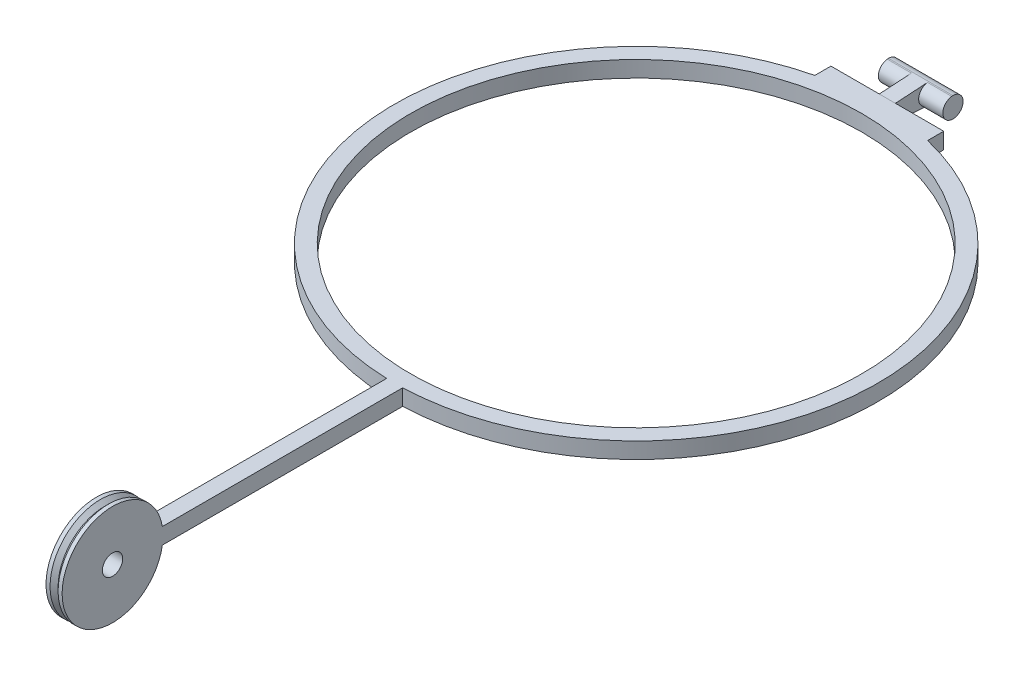
SolidWorks part; units mm, degrees
ref_plane "Front Plane" through (0, 0, 0) normal (0, 0, 1) x (1, 0, 0)
ref_plane "Top Plane" through (0, 0, 0) normal (0, 1, 0) x (1, 0, 0)
ref_plane "Right Plane" through (0, 0, 0) normal (1, 0, 0) x (0, 0, -1)
sketch "Sketch1" plane through (0, 0, 0) normal (0, 0, 1) x (1, 0, 0)
  line L0 (0, 0) -> (11.6505, 0) construction
  line L1 (0, 4) -> (6.35, 4)
  line L2 (0, 0) -> (0, 4) construction
  line L3 (0, 4) -> (0, 19.875)
  line L6 (6.35, 19.875) -> (6.35, 4)
  line L7 (3.175, 4) -> (3.175, 18.2875) construction
  line L8 (0, 19.875) -> (1.5875, 19.875)
  line L9 (1.5875, 19.875) -> (3.175, 18.2875)
  line L10 (4.7625, 19.875) -> (3.175, 18.2875)
  line L11 (6.35, 19.875) -> (4.7625, 19.875)
  dimension "D1" = 6.35
  dimension "D2" = 8
  dimension "D3" = 1.5875
  dimension "D4" = 15.875
  dimension "D5" = 1.5875
revolve "Revolve1" add sketch "Sketch1" angle 360 about L0
sketch "Sketch2" plane through (6.35, 0, 0) normal (1, 0, 0) x (0, 0, -1)
  line L0 (0, 0) -> (304.8, 0) construction
  line L1 (20.0281, 3.175) -> (304.8, 3.175)
  line L2 (304.8, 3.175) -> (304.8, 0)
  line L3 (20.0281, -3.175) -> (304.8, -3.175)
  line L4 (304.8, -3.175) -> (304.8, 0)
  circle A0 centre (0, 0) radius 4 construction
  circle A1 centre (0, 0) radius 4
  arc A7 (17.5856, 5.018) -> (17.5856, -5.018) centre (0, 0) ccw
  arc A8 (20.0281, -3.175) -> (17.5856, -5.018) centre (20.0281, -5.715) ccw
  arc A9 (20.0281, 3.175) -> (17.5856, 5.018) centre (20.0281, 5.715) cw
  circle A10 centre (0, 0) radius 18.2875 construction
  dimension "D3" = 2.54
  dimension "D1" = 304.8
  dimension "D2" = 6.35
extrude "Boss-Extrude1" add sketch "Sketch2" against normal up to surface (6.35 mm away) up to face at (0, 0, 4)
sketch "Sketch5" plane through (0, 3.175, 0) normal (0, 1, 0) x (1, 0, 0)
  line L0 (6.35, 304.8) -> (6.35, 20.0281) construction
  line L1 (0, 304.8) -> (6.35, 304.8)
  line L2 (0, 304.8) -> (0, 366.2512)
  line L3 (0, 366.2512) -> (6.35, 366.2512)
  line L4 (6.35, 304.8) -> (6.35, 366.2512)
extrude "Boss-Extrude3" [suppressed] add sketch "Sketch5" along normal blind 228.6
sketch "Sketch6" plane through (0, -3.175, 0) normal (0, -1, 0) x (1, 0, 0)
  line L0 (3.175, -298.45) -> (3.175, -43.3369) construction
  line L2 (0, -304.8) -> (0, -20.0281) construction
  line L3 (6.35, -20.0281) -> (6.35, -304.8) construction
  line L4 (-19.05, -302.1708) -> (-19.05, -308.5208)
  line L5 (-19.05, -308.5208) -> (25.4, -308.5208)
  line L6 (25.4, -308.5208) -> (25.4, -302.1708)
  line L7 (0, -304.8) -> (6.35, -304.8) construction
  circle A0 centre (3.175, -209.55) radius 88.9
  circle A1 centre (3.175, -209.55) radius 95.25
  line M2 (0, -20.0281) -> (0, -304.8)
  line M3 (0, -304.8) -> (6.35, -304.8)
  line M4 (6.35, -304.8) -> (6.35, -20.0281)
  dimension "D4" = 177.8
  dimension "D2" = 6.35
  dimension "D3" = 44.45
  dimension "D1" = 6.35
extrude "Boss-Extrude4" add sketch "Sketch6" against normal blind 6.35 contours A1 A0 M2 | A1 A0 M4 | A1 L4 L5 L6 M4 M3 M2 region at (3.175, -3.175, -306.1588) region at (-89.4847, -3.175, -200.1517) region at (70.1201, -3.175, -144.8004)
extrude "Cut-Extrude1" cut sketch "Sketch6<4>" against normal through all both and the other way through all contours A0 L0 M2 | L0 A0 M4 region at (1.5877, -3.175, -209.55) region at (4.7623, -3.175, -209.55)
sketch "Sketch6<4>" plane through (0, -3.175, 0) normal (0, -1, 0) x (1, 0, 0) same geometry as "Sketch6"
ref_plane "Plane1" through (3.175, 0, 0) normal (-1, 0, 0) x (0, 0, 1)
sketch "Sketch8" plane through (3.175, 0, 0) normal (-1, 0, 0) x (0, 0, 1)
  line L0 (-302.1708, 0) -> (-321.6833, 0) construction
  line L1 (-308.5208, 3.175) -> (-321.6833, 4)
  line L2 (-308.5208, -3.175) -> (-321.6833, -4)
  line L4 (-308.5208, -3.175) -> (-302.1708, -3.175)
  line L5 (-302.1708, -3.175) -> (-302.1708, 3.175)
  line L6 (-302.1708, 3.175) -> (-308.5208, 3.175)
  line L7 (-308.5208, 3.175) -> (-308.5208, -3.175)
  line L8 (-308.5208, -3.175) -> (-302.1708, -3.175)
  line L9 (-302.1708, -3.175) -> (-302.1708, 3.175)
  line L10 (-302.1708, 3.175) -> (-308.5208, 3.175)
  line L11 (-308.5208, 3.175) -> (-308.5208, -3.175)
  circle A0 centre (-321.6833, 0) radius 11 construction
  circle A1 centre (-321.6833, 0) radius 13.54 construction
  circle A2 centre (-321.6833, 0) radius 4
  dimension "D2" = 22
  dimension "D4" = 8
  dimension "D1" = 0
  dimension "D3" = 2.54
extrude "Boss-Extrude5" add sketch "Sketch8" along normal mid plane 6.35 contours A2 L2 L11 L1 region at (3.175, 0, -313.6754)
extrude "Boss-Extrude6" add sketch "Sketch8<3>" along normal mid plane 25.4 contours L1 A2 L2 region at (3.175, 0, -321.6833)
sketch "Sketch8<3>" plane through (3.175, 0, 0) normal (-1, 0, 0) x (0, 0, 1) same geometry as "Sketch8"
